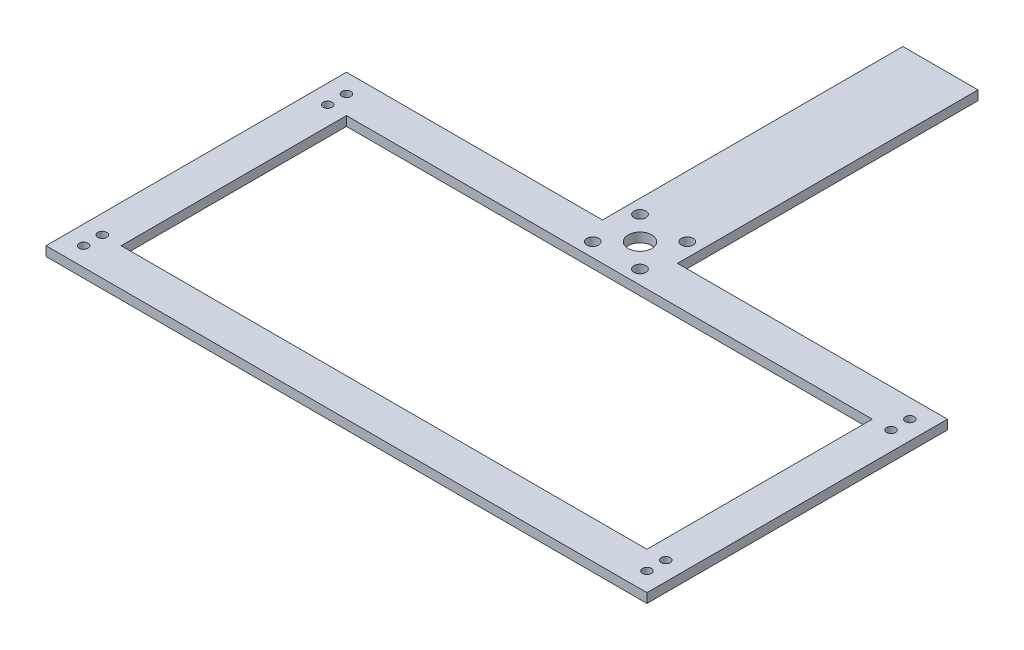
SolidWorks part; units mm, degrees
ref_plane "Front" through (0, 0, 0) normal (0, 0, 1) x (1, 0, 0)
ref_plane "Top" through (0, 0, 0) normal (0, 1, 0) x (1, 0, 0)
ref_plane "Right" through (0, 0, 0) normal (1, 0, 0) x (0, 0, -1)
sketch "Sketch1" plane through (0, 0, 0) normal (0, 1, 0) x (1, 0, 0)
  line L0 (6.35, 101.6) -> (6.35, 95.25)
  line L1 (0, 0) -> (203.2, 0)
  line L2 (0, 0) -> (0, 101.6)
  line L3 (0, 101.6) -> (203.2, 101.6)
  line L4 (203.2, 0) -> (203.2, 101.6)
  line L5 (12.7, 88.9) -> (190.5, 88.9)
  line L6 (12.7, 88.9) -> (12.7, 12.7)
  line L7 (12.7, 12.7) -> (190.5, 12.7)
  line L8 (190.5, 88.9) -> (190.5, 12.7)
  line L9 (6.35, 95.25) -> (6.35, 88.9)
  line L10 (12.7, 50.8) -> (0, 50.8)
  line L11 (101.6, 12.7) -> (101.6, 0)
  line L13 (86.5462, 101.6) -> (111.9462, 101.6)
  line L14 (86.5462, 101.6) -> (86.5462, 203.2)
  line L15 (86.5462, 203.2) -> (111.9462, 203.2)
  line L16 (111.9462, 101.6) -> (111.9462, 203.2)
  circle A0 centre (6.35, 95.25) radius 1.5
  circle A1 centre (6.35, 88.9) radius 1.5
  circle A2 centre (6.35, 6.35) radius 1.5
  circle A3 centre (6.35, 12.7) radius 1.5
  circle A4 centre (196.85, 95.25) radius 1.5
  circle A5 centre (196.85, 88.9) radius 1.5
  circle A6 centre (196.85, 12.7) radius 1.5
  circle A7 centre (196.85, 6.35) radius 1.5
  dimension "D10" = 25.4
  dimension "D1" = 101.6
  dimension "D2" = 203.2
  dimension "D3" = 12.7
  dimension "D4" = 12.7
  dimension "D5" = 12.7
  dimension "D6" = 12.7
  dimension "D7" = 6.35
  dimension "D8" = 6.35
  dimension "D9" = 6.35
  dimension "D11" = 101.6
extrude "Boss-Extrude1" add sketch "Sketch1" along normal blind 3.175 contours A1 A0 L3 L2 L10 L6 L5 L8 L7 L11 L1 L4 A7 A6 A4 A5 | L11 L7 L6 L10 L2 L1 A2 A3 | L3 L16 L15 L14 region at (46.4481, 0, -99.3282) region at (99.2462, 0, -152.4) region at (6.35, 0, -49.6641)
sketch "Sketch2" plane through (0, 3.175, 0) normal (0, 1, 0) x (1, 0, 0)
  line L0 (86.5462, 101.6) -> (111.9462, 101.6)
  line L1 (91.2462, 93.6) -> (107.2462, 109.6)
  line L2 (91.2462, 109.6) -> (107.2462, 93.6)
  circle A0 centre (99.2462, 101.6) radius 11.3137
  circle A1 centre (91.2462, 109.6) radius 2
  circle A2 centre (107.2462, 109.6) radius 2
  circle A3 centre (91.2462, 93.6) radius 2
  circle A4 centre (107.2462, 93.6) radius 2
  circle A5 centre (99.2462, 101.6) radius 4
  point P9 (99.2462, 101.6)
  point P12 (99.2462, 101.6)
extrude "Cut-Extrude1" cut sketch "Sketch2" against normal blind 3.175 contours A0 A2 | L1 A2 A0 | A0 A2 L1 | A1 | A3 | A4 | A5 region at (107.2063, 3.175, -108.3956) region at (107.8233, 3.175, -110.1771) region at (106.0418, 3.175, -109.5601)
